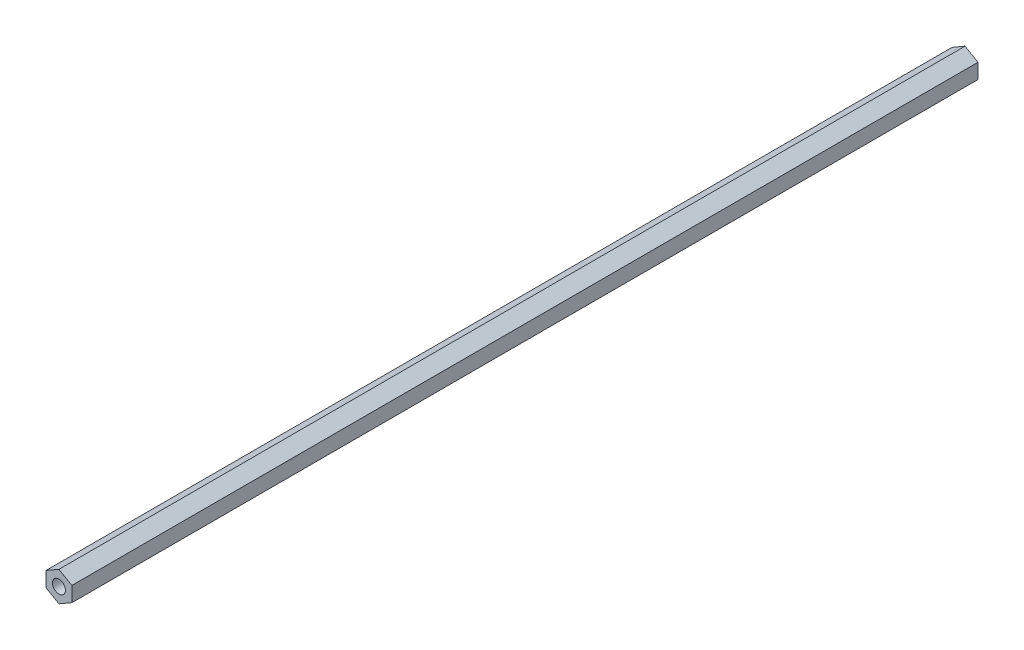
SolidWorks part; units mm, degrees
material "6061 Alloy"
ref_plane "Front Plane" through (0, 0, 0) normal (0, 0, 1) x (1, 0, 0)
ref_plane "Top Plane" through (0, 0, 0) normal (0, 1, 0) x (1, 0, 0)
ref_plane "Right Plane" through (0, 0, 0) normal (1, 0, 0) x (0, 0, -1)
sketch "Sketch1" plane through (0, 0, 0) normal (0, 0, 1) x (1, 0, 0)
  line L1 (0, 7.3323) -> (-6.35, 3.6662) construction
  line L2 (-6.35, 3.6662) -> (-6.35, -3.6662) construction
  line L3 (-6.35, -3.6662) -> (0, -7.3323) construction
  line L4 (0, -7.3323) -> (6.35, -3.6662) construction
  line L5 (6.35, -3.6662) -> (6.35, 3.6662) construction
  line L6 (6.35, 3.6662) -> (0, 7.3323) construction
  circle A2 centre (0, 0) radius 6.35 construction
  dimension "Width" = 12.7
sketch "Sketch2" plane through (0, 0, 0) normal (1, 0, 0) x (0, 0, -1)
  line L0 (-222.25, 7.3323) -> (222.25, 7.3323) construction
  point P2 (0, 7.3323)
  point P3 (190.5, 7.3323)
  point P4 (-190.5, 7.3323)
  dimension "Length" = 444.5
  dimension "D2" = 31.75
  dimension "D1" = 31.75
sketch "Sketch3" plane through (0, 0, 0) normal (0, 0, 1) x (1, 0, 0)
  line L0 (-6.35, -3.6662) -> (0, -7.3323) construction
  line L1 (0, -7.3323) -> (6.35, -3.6662) construction
  line L2 (6.35, -3.6662) -> (6.35, 3.6662) construction
  line L3 (6.35, 3.6662) -> (0, 7.3323) construction
  line L4 (0, 7.3323) -> (-6.35, 3.6662) construction
  line L5 (-6.35, 3.6662) -> (-6.35, -3.6662) construction
  line L6 (-6.35, -3.6662) -> (0, -7.3323)
  line L7 (0, -7.3323) -> (6.35, -3.6662)
  line L8 (6.35, -3.6662) -> (6.35, 3.6662)
  line L9 (6.35, 3.6662) -> (0, 7.3323)
  line L10 (0, 7.3323) -> (-6.35, 3.6662)
  line L11 (-6.35, 3.6662) -> (-6.35, -3.6662)
extrude "Boss-Extrude2" add sketch "Sketch3" along normal up to vertex (222.25 mm away) and the other way up to vertex (222.25 mm away) up to point (0, 7.3323, 222.25) other way up to point (0, 7.3323, -222.25)
sketch "Sketch4" plane through (0, 0, 222.25) normal (0, 0, 1) x (1, 0, 0)
  point P0 (0, 0)
hole_wizard "1/4 (0.25) Diameter Hole1" positions "Sketch5" profile "Sketch6" hole size "1/4" standard "ANSI Inch"
sketch "Sketch5" plane through (0, 0, 222.25) normal (0, 0, 1) x (1, 0, 0)
  point P0 (0, 0)
sketch "Sketch6" plane through (0, 0, 222.25) normal (1, 0, 0) x (0, -1, 0)
  line L0 (0, 0) -> (0, 27.3077)
  line L1 (0, 27.3077) -> (3.175, 25.4)
  line L2 (3.175, 25.4) -> (3.175, 0)
  line L5 (3.175, 0) -> (0, 0)
  line L10 (0, 27.3077) -> (-3.175, 25.4) construction
  line L11 (0, -6.35) -> (0, 107.95) construction
  dimension "Hole Dia." = 6.35
  dimension "Hole Depth" = 25.4
  dimension "Drill Angle" = 118
hole_wizard "1/4 (0.25) Diameter Hole2" positions "Sketch7" profile "Sketch8" hole size "1/4" standard "ANSI Inch"
sketch "Sketch7" plane through (0, 0, -222.25) normal (0, 0, -1) x (-1, 0, 0)
  point P0 (0, 0)
sketch "Sketch8" plane through (0, 0, -222.25) normal (1, 0, 0) x (0, 1, 0)
  line L0 (0, 0) -> (0, 27.3077)
  line L1 (0, 27.3077) -> (3.175, 25.4)
  line L2 (3.175, 25.4) -> (3.175, 0)
  line L5 (3.175, 0) -> (0, 0)
  line L10 (0, 27.3077) -> (-3.175, 25.4) construction
  line L11 (0, -6.35) -> (0, 107.95) construction
  dimension "Hole Dia." = 6.35
  dimension "Hole Depth" = 25.4
  dimension "Drill Angle" = 118
equation "\"D2@Sketch2\" = \"D1@Sketch2\""
equation "\"D1@Sketch2\" = \"Width@Sketch1\" * 2.5"
